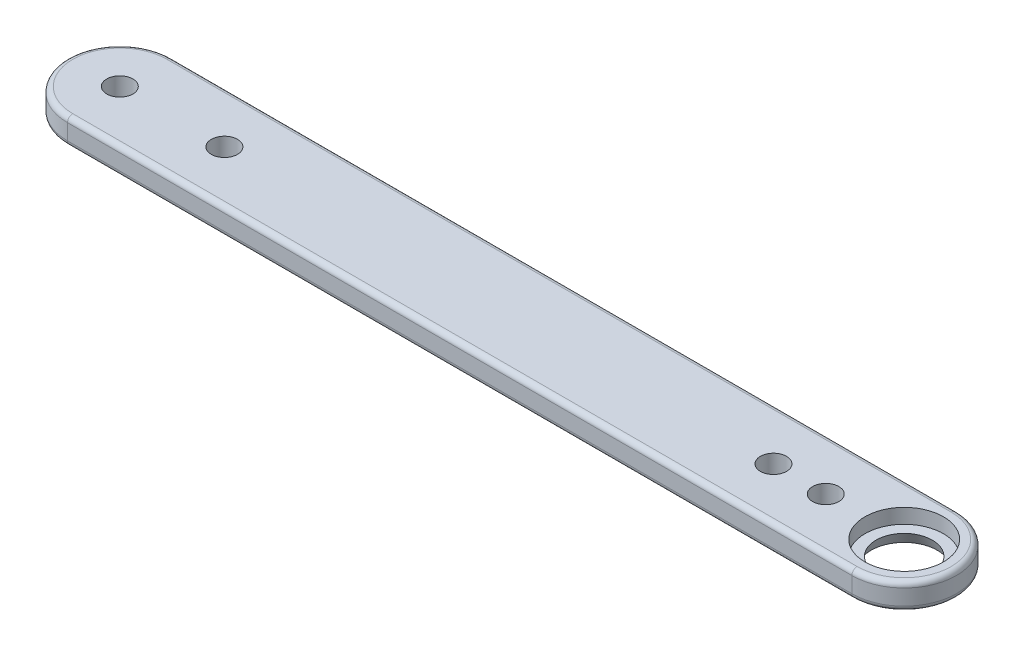
SolidWorks part; units mm, degrees
material "Plain Carbon Steel"
ref_plane "Front Plane" through (0, 0, 0) normal (0, 0, 1) x (1, 0, 0)
ref_plane "Top Plane" through (0, 0, 0) normal (0, 1, 0) x (1, 0, 0)
ref_plane "Right Plane" through (0, 0, 0) normal (1, 0, 0) x (0, 0, -1)
sketch "Sketch1" plane through (0, 0, 0) normal (0, 1, 0) x (1, 0, 0)
  line L1 (107.95, -12.7) -> (-107.95, -12.7)
  line L2 (107.95, -12.7) -> (107.95, 12.7)
  line L3 (107.95, 12.7) -> (-107.95, 12.7)
  line L4 (-107.95, -12.7) -> (-107.95, 12.7)
  line L5 (107.95, -12.7) -> (-107.95, 12.7) construction
  line L6 (107.95, 12.7) -> (-107.95, -12.7) construction
  point P0 (0, 0)
  dimension "D1" = 25.4
  dimension "D2" = 215.9
extrude "Boss-Extrude1" add sketch "Sketch1" along normal blind 6.35
sketch "Sketch2" plane through (0, 6.35, 0) normal (0, 1, 0) x (1, 0, 0)
  line L0 (-107.95, 0) -> (107.95, 0) construction
  line L1 (-107.95, 12.7) -> (-107.95, -12.7) construction
  line L2 (107.95, -12.7) -> (107.95, 12.7) construction
  circle A0 centre (-95.25, 0) radius 3.175
  circle A3 centre (95.25, 0) radius 6.35
  circle A7 centre (-69.85, 0) radius 3.175
  dimension "D1" = 12.7
  dimension "D4" = 6.35
  dimension "D2" = 190.5
  dimension "D3" = 12.7
  dimension "D5" = 2
extrude "Cut-Extrude1" cut sketch "Sketch2" against normal through all
sketch "Sketch3" plane through (0, 6.35, 0) normal (0, 1, 0) x (1, 0, 0)
  circle A0 centre (95.25, 0) radius 9.525
  dimension "D1" = 19.05
extrude "Cut-Extrude2" cut sketch "Sketch3" against normal blind 3.5719
sketch "Sketch4" plane through (0, 6.35, 0) normal (0, 1, 0) x (1, 0, 0)
  line L0 (-107.95, 0) -> (107.95, 0) construction
  circle A0 centre (76.2, 0) radius 3.175
  circle A2 centre (63.5, 0) radius 3.175
  dimension "D3" = 6.35
  dimension "D1" = 19.05
  dimension "D2" = 12.7
extrude "Cut-Extrude3" cut sketch "Sketch4" against normal through all
sketch "Sketch5" plane through (0, 6.35, 0) normal (0, 1, 0) x (1, 0, 0)
  line L3 (-107.95, 12.7) -> (-107.95, -12.7) construction
  line L8 (107.95, -12.7) -> (107.95, 12.7) construction
  circle A1 centre (95.25, 0) radius 12.7
  circle A2 centre (-95.25, 0) radius 12.7
  line M11 (107.95, -12.7) -> (107.95, 12.7)
  line M13 (-107.95, 12.7) -> (-107.95, -12.7)
  line M25 (-107.95, -12.7) -> (107.95, -12.7)
  line M26 (107.95, 12.7) -> (-107.95, 12.7)
extrude "Cut-Extrude4" cut sketch "Sketch5" against normal through all contours A1 M11 M26 | A1 M25 M11 | A2 M26 M13 | A2 M13 M25 region at (105.1132, 6.35, 9.8632) region at (105.1132, 6.35, -9.8632) region at (-105.1132, 6.35, -9.8632) region at (-105.1132, 6.35, 9.8632)
fillet "Fillet1" radius 1.27 8 edges at (0, 0, -12.7) (0, 6.35, -12.7) (0, 0, 12.7) (0, 6.35, 12.7) (-107.95, 0, 0) (-107.95, 6.35, 0) (107.95, 0, 0) (107.95, 6.35, 0)
ref_axis "Axis1" through (95.25, 0, 0) along (0, 1, 0)
ref_plane "Plane1" through (95.25, 0, 0) normal (-1, 0, 0) x (0, 0, 1)
sketch "Sketch6" plane through (95.25, 0, 0) normal (-1, 0, 0) x (0, 0, 1)
  line L0 (0, 0) -> (0, 6.35)
  line L1 (11.43, 6.35) -> (-11.43, 6.35) construction
  line L2 (0, 6.35) -> (-3.6942, -1.9474)
  line L3 (-3.6942, -1.9474) -> (-8.0682, 0)
  line L4 (-8.0682, 0) -> (-4.374, 8.2974)
  line L5 (-4.374, 8.2974) -> (0, 6.35)
  line L6 (-11.43, 0) -> (11.43, 0) construction
  line L7 (0, 0) -> (-6.35, 0)
  line L8 (-6.35, 0) -> (-6.35, 2.7781)
  line L9 (-6.35, 2.7781) -> (0, 2.7781)
  line L10 (-6.35, 0) -> (-8.0682, 0)
  line L11 (-6.35, 2.7781) -> (-6.8313, 2.7781)
  dimension "D1" = 24
  dimension "D2" = 4.7879
  dimension "D3" = 6.35
  dimension "D4" = 2.7781
revolve "Cut-Revolve2" cut sketch "Sketch6" angle 360 about axis through (95.25, 0, 0) along (0, 1, 0) region at (95.25, 1.1287, -6.9578)
